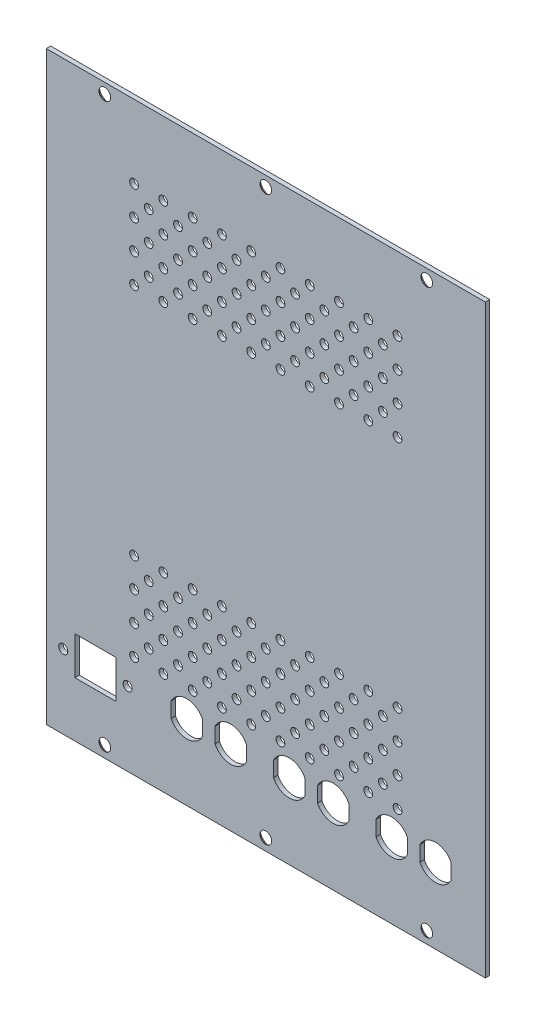
SolidWorks part; units mm, degrees
ref_plane "Спереди" through (0, 0, 0) normal (0, 0, 1) x (1, 0, 0)
ref_plane "Сверху" through (0, 0, 0) normal (0, 1, 0) x (1, 0, 0)
ref_plane "Справа" through (0, 0, 0) normal (1, 0, 0) x (0, 0, -1)
sketch "Эскиз1" plane through (0, 0, 0) normal (0, 0, 1) x (1, 0, 0)
  line L1 (0, 0) -> (150, 0)
  line L2 (0, 0) -> (0, 200)
  line L3 (0, 200) -> (150, 200)
  line L4 (150, 0) -> (150, 200)
  dimension "D1" = 150
  dimension "D2" = 200
extrude "Бобышка-Вытянуть1" add sketch "Эскиз1" along normal blind 1.5
sketch "Эскиз2" plane through (0, 0, 1.5) normal (0, 0, 1) x (1, 0, 0)
  line L0 (0, 0) -> (150, 0) construction
  line L1 (0, 200) -> (0, 0) construction
  line L2 (150, 200) -> (0, 200) construction
  circle A0 centre (20, 196.5) radius 2
  circle A1 centre (20, 4) radius 2
  circle A2 centre (75, 196.5) radius 2
  circle A3 centre (75, 4) radius 2
  circle A4 centre (130, 196.5) radius 2
  circle A5 centre (130, 4) radius 2
  dimension "D1" = 4
  dimension "D2" = 4
  dimension "D3" = 20
  dimension "D4" = 3.5
  dimension "D5" = 3
extrude "Вырез-Вытянуть1" cut sketch "Эскиз2" against normal through all
sketch "Эскиз3" plane through (0, 0, 1.5) normal (0, 0, 1) x (1, 0, 0)
  line L0 (0, 200) -> (0, 0) construction
  line L1 (0, 0) -> (150, 0) construction
  circle A0 centre (30, 35) radius 1.5
  circle A1 centre (40, 35) radius 1.5
  circle A2 centre (50, 35) radius 1.5
  circle A3 centre (60, 35) radius 1.5
  circle A4 centre (70, 35) radius 1.5
  circle A5 centre (80, 35) radius 1.5
  circle A6 centre (90, 35) radius 1.5
  circle A7 centre (100, 35) radius 1.5
  circle A8 centre (110, 35) radius 1.5
  circle A9 centre (120, 35) radius 1.5
  circle A10 centre (30, 45) radius 1.5
  circle A11 centre (40, 45) radius 1.5
  circle A12 centre (50, 45) radius 1.5
  circle A13 centre (60, 45) radius 1.5
  circle A14 centre (70, 45) radius 1.5
  circle A15 centre (80, 45) radius 1.5
  circle A16 centre (90, 45) radius 1.5
  circle A17 centre (100, 45) radius 1.5
  circle A18 centre (110, 45) radius 1.5
  circle A19 centre (120, 45) radius 1.5
  circle A20 centre (30, 55) radius 1.5
  circle A21 centre (40, 55) radius 1.5
  circle A22 centre (50, 55) radius 1.5
  circle A23 centre (60, 55) radius 1.5
  circle A24 centre (70, 55) radius 1.5
  circle A25 centre (80, 55) radius 1.5
  circle A26 centre (90, 55) radius 1.5
  circle A27 centre (100, 55) radius 1.5
  circle A28 centre (110, 55) radius 1.5
  circle A29 centre (120, 55) radius 1.5
  circle A30 centre (30, 65) radius 1.5
  circle A31 centre (40, 65) radius 1.5
  circle A32 centre (50, 65) radius 1.5
  circle A33 centre (60, 65) radius 1.5
  circle A34 centre (70, 65) radius 1.5
  circle A35 centre (80, 65) radius 1.5
  circle A36 centre (90, 65) radius 1.5
  circle A37 centre (100, 65) radius 1.5
  circle A38 centre (110, 65) radius 1.5
  circle A39 centre (120, 65) radius 1.5
  circle A40 centre (35, 40) radius 1.5
  circle A41 centre (45, 40) radius 1.5
  circle A42 centre (55, 40) radius 1.5
  circle A43 centre (65, 40) radius 1.5
  circle A44 centre (75, 40) radius 1.5
  circle A45 centre (85, 40) radius 1.5
  circle A46 centre (95, 40) radius 1.5
  circle A47 centre (105, 40) radius 1.5
  circle A48 centre (115, 40) radius 1.5
  circle A49 centre (45, 50) radius 1.5
  circle A50 centre (55, 50) radius 1.5
  circle A51 centre (65, 50) radius 1.5
  circle A52 centre (75, 50) radius 1.5
  circle A53 centre (85, 50) radius 1.5
  circle A54 centre (95, 50) radius 1.5
  circle A55 centre (105, 50) radius 1.5
  circle A56 centre (115, 50) radius 1.5
  circle A57 centre (45, 60) radius 1.5
  circle A58 centre (55, 60) radius 1.5
  circle A59 centre (65, 60) radius 1.5
  circle A60 centre (75, 60) radius 1.5
  circle A61 centre (85, 60) radius 1.5
  circle A62 centre (95, 60) radius 1.5
  circle A63 centre (105, 60) radius 1.5
  circle A64 centre (115, 60) radius 1.5
  circle A65 centre (35, 50) radius 1.5
  circle A66 centre (35, 60) radius 1.5
  circle A67 centre (30, 145) radius 1.5
  circle A68 centre (40, 145) radius 1.5
  circle A69 centre (50, 145) radius 1.5
  circle A70 centre (60, 145) radius 1.5
  circle A71 centre (70, 145) radius 1.5
  circle A72 centre (80, 145) radius 1.5
  circle A73 centre (90, 145) radius 1.5
  circle A74 centre (100, 145) radius 1.5
  circle A75 centre (110, 145) radius 1.5
  circle A76 centre (120, 145) radius 1.5
  circle A77 centre (30, 155) radius 1.5
  circle A78 centre (40, 155) radius 1.5
  circle A79 centre (50, 155) radius 1.5
  circle A80 centre (60, 155) radius 1.5
  circle A81 centre (70, 155) radius 1.5
  circle A82 centre (80, 155) radius 1.5
  circle A83 centre (90, 155) radius 1.5
  circle A84 centre (100, 155) radius 1.5
  circle A85 centre (110, 155) radius 1.5
  circle A86 centre (120, 155) radius 1.5
  circle A87 centre (30, 165) radius 1.5
  circle A88 centre (40, 165) radius 1.5
  circle A89 centre (50, 165) radius 1.5
  circle A90 centre (60, 165) radius 1.5
  circle A91 centre (70, 165) radius 1.5
  circle A92 centre (80, 165) radius 1.5
  circle A93 centre (90, 165) radius 1.5
  circle A94 centre (100, 165) radius 1.5
  circle A95 centre (110, 165) radius 1.5
  circle A96 centre (120, 165) radius 1.5
  circle A97 centre (30, 175) radius 1.5
  circle A98 centre (40, 175) radius 1.5
  circle A99 centre (50, 175) radius 1.5
  circle A100 centre (60, 175) radius 1.5
  circle A101 centre (70, 175) radius 1.5
  circle A102 centre (80, 175) radius 1.5
  circle A103 centre (90, 175) radius 1.5
  circle A104 centre (100, 175) radius 1.5
  circle A105 centre (110, 175) radius 1.5
  circle A106 centre (120, 175) radius 1.5
  circle A107 centre (35, 150) radius 1.5
  circle A108 centre (45, 150) radius 1.5
  circle A109 centre (55, 150) radius 1.5
  circle A110 centre (65, 150) radius 1.5
  circle A111 centre (75, 150) radius 1.5
  circle A112 centre (85, 150) radius 1.5
  circle A113 centre (95, 150) radius 1.5
  circle A114 centre (105, 150) radius 1.5
  circle A115 centre (115, 150) radius 1.5
  circle A116 centre (45, 160) radius 1.5
  circle A117 centre (55, 160) radius 1.5
  circle A118 centre (65, 160) radius 1.5
  circle A119 centre (75, 160) radius 1.5
  circle A120 centre (85, 160) radius 1.5
  circle A121 centre (95, 160) radius 1.5
  circle A122 centre (105, 160) radius 1.5
  circle A123 centre (115, 160) radius 1.5
  circle A124 centre (45, 170) radius 1.5
  circle A125 centre (55, 170) radius 1.5
  circle A126 centre (65, 170) radius 1.5
  circle A127 centre (75, 170) radius 1.5
  circle A128 centre (85, 170) radius 1.5
  circle A129 centre (95, 170) radius 1.5
  circle A130 centre (105, 170) radius 1.5
  circle A131 centre (115, 170) radius 1.5
  circle A132 centre (35, 160) radius 1.5
  circle A133 centre (35, 170) radius 1.5
  dimension "D1" = 3
  dimension "D2" = 30
  dimension "D3" = 35
  dimension "D5" = 4
  dimension "D6" = 5
  dimension "D7" = 5
  dimension "D4" = 10
  dimension "D8" = 9
  dimension "D9" = 3
  dimension "D10" = 2
extrude "Вырез-Вытянуть2" cut sketch "Эскиз3" against normal through all
sketch "Эскиз4" plane through (0, 0, 0) normal (0, 0, -1) x (-1, 0, 0)
  line L0 (-150, 0) -> (-150, 200) construction
  line L1 (0, 0) -> (-150, 0) construction
  circle A0 centre (-48, 25) radius 4.85
  circle A1 centre (-133, 25) radius 4.85
  circle A2 centre (-118, 25) radius 4.85
  circle A3 centre (-83, 25) radius 4.85
  circle A4 centre (-98, 25) radius 4.85
  circle A5 centre (-63, 25) radius 4.85
  dimension "D1" = 9.7
  dimension "D2" = 17
  dimension "D3" = 25
  dimension "D4" = 2
  dimension "D5" = 3
extrude "Вырез-Вытянуть3" cut sketch "Эскиз4" against normal through all
sketch "Эскиз5" plane through (0, 0, 0) normal (0, 0, -1) x (-1, 0, 0)
  line L0 (-131, 13) -> (-116.6472, 13) construction
  line L1 (-96, 13) -> (-81.6472, 13) construction
  line L2 (0, 0) -> (-150, 0) construction
  line L3 (-73, 13) -> (-10.6742, 13) construction
  circle A0 centre (-133, 25) radius 4.85 construction
  circle A1 centre (-98, 25) radius 4.85 construction
  circle A2 centre (-63, 25) radius 4.85 construction
  text T0 "24V" font "GOST Type BU" height 5
  text T1 "10V" font "GOST type B" height 5
  text T2 "мультиметр" font "GOST type B" height 5
  dimension "D1" = 13
  dimension "D2" = 2
  dimension "D3" = 2
  dimension "D4" = 10
extrude "Вырез-Вытянуть4" cut sketch "Эскиз5" against normal blind 0.5
sketch "Эскиз8" plane through (0, 0, 0) normal (0, 0, -1) x (-1, 0, 0)
  line L0 (0, 200) -> (0, 0) construction
  line L1 (-21, 31.05) -> (-10, 31.05)
  line L2 (-21, 31.05) -> (-21, 18.95)
  line L3 (-21, 18.95) -> (-10, 18.95)
  line L4 (-10, 31.05) -> (-10, 18.95)
  circle A1 centre (-48, 25) radius 4.85 construction
  point P6 (-21, 25)
  dimension "D1" = 10
  dimension "D2" = 0
  dimension "D3" = 11
  dimension "D4" = 12.1
extrude "Вырез-Вытянуть5" cut sketch "Эскиз8" against normal through all
sketch "Эскиз9" plane through (0, 0, 0) normal (0, 0, -1) x (-1, 0, 0)
  line L0 (-22.5, 10.95) -> (-5.209, 10.95) construction
  line L1 (-21, 18.95) -> (-10, 18.95) construction
  line L2 (-21, 31.05) -> (-21, 18.95) construction
  text T0 "USB" font "GOST type B" height 6
  dimension "D1" = 8
  dimension "D2" = 1.5
extrude "Вырез-Вытянуть6" cut sketch "Эскиз9" against normal up to surface (0.5 mm away) up to face at (36.6786, 14.7184, 0.5)
chamfer "Фаска1" distance 1.4 angle 45 6 edges at (22, 4, 0) (77, 4, 0) (132, 4, 0) (22, 196.5, 0) (77, 196.5, 0) (132, 196.5, 0)
sketch "Эскиз10" plane through (0, 0, 0) normal (0, 0, -1) x (-1, 0, 0)
  line L0 (0, 0) -> (-150, 0) construction
  line L1 (-103.35, 28.3038) -> (-103.35, 23.0962)
  line L2 (-138.35, 35.1494) -> (-127.65, 35.1494) construction
  line L3 (-138.35, 28.3038) -> (-138.35, 23.0962)
  line L4 (-138.35, 18.1769) -> (-127.65, 18.1769) construction
  line L5 (-127.65, 28.3038) -> (-127.65, 23.0962)
  line L6 (-123.35, 36.7729) -> (-112.65, 36.7729) construction
  line L7 (-123.35, 28.3038) -> (-123.35, 23.0962)
  line L8 (-123.35, 17.0454) -> (-112.65, 17.0454) construction
  line L9 (-112.65, 28.3038) -> (-112.65, 23.0962)
  line L10 (-92.65, 28.3038) -> (-92.65, 23.0962)
  line L11 (-88.35, 28.3038) -> (-88.35, 23.0962)
  line L12 (-77.65, 28.3038) -> (-77.65, 23.0962)
  line L13 (-68.35, 28.3038) -> (-68.35, 23.0962)
  line L14 (-57.65, 28.3038) -> (-57.65, 23.0962)
  line L15 (-53.35, 28.3038) -> (-53.35, 23.0962)
  line L16 (-42.65, 28.3038) -> (-42.65, 23.0962)
  arc A0 (-138.35, 23.0962) -> (-127.65, 23.0962) centre (-133, 25.7) ccw
  arc A1 (-112.65, 28.3038) -> (-123.35, 28.3038) centre (-118, 25.7) ccw
  arc A2 (-127.65, 28.3038) -> (-138.35, 28.3038) centre (-133, 25.7) ccw
  circle A3 centre (-133, 25) radius 4.85 construction
  circle A4 centre (-118, 25) radius 4.85 construction
  arc A5 (-123.35, 23.0962) -> (-112.65, 23.0962) centre (-118, 25.7) ccw
  arc A6 (-92.65, 28.3038) -> (-103.35, 28.3038) centre (-98, 25.7) ccw
  arc A7 (-103.35, 23.0962) -> (-92.65, 23.0962) centre (-98, 25.7) ccw
  arc A8 (-77.65, 28.3038) -> (-88.35, 28.3038) centre (-83, 25.7) ccw
  arc A9 (-88.35, 23.0962) -> (-77.65, 23.0962) centre (-83, 25.7) ccw
  arc A10 (-57.65, 28.3038) -> (-68.35, 28.3038) centre (-63, 25.7) ccw
  arc A11 (-68.35, 23.0962) -> (-57.65, 23.0962) centre (-63, 25.7) ccw
  arc A12 (-42.65, 28.3038) -> (-53.35, 28.3038) centre (-48, 25.7) ccw
  arc A13 (-53.35, 23.0962) -> (-42.65, 23.0962) centre (-48, 25.7) ccw
  point P14 (-133, 18.1769)
  point P22 (-118, 17.0454)
  dimension "D1" = 11.9
  dimension "D5" = 10.7
  dimension "D7" = 0
  dimension "D2" = 0
  dimension "D3" = 0
  dimension "D4" = 25.7
  dimension "D6" = 0
  dimension "D8" = 3
extrude "Вырез-Вытянуть7" cut sketch "Эскиз10" against normal through all
sketch "Эскиз11" plane through (0, 0, 0) normal (0, 0, -1) x (-1, 0, 0)
  line L0 (-21, 18.95) -> (-10, 18.95) construction
  line L1 (-23.8, 31.75) -> (-9.8, 31.75)
  line L2 (-23.8, 31.75) -> (-23.8, 18.75)
  line L3 (-23.8, 18.75) -> (-9.8, 18.75)
  line L4 (-9.8, 31.75) -> (-9.8, 18.75)
  line L5 (-10, 18.95) -> (-10, 31.05) construction
  point P4 (-23.4568, 18.5694)
  dimension "D1" = 14
  dimension "D2" = 13
  dimension "D3" = 0.2
  dimension "D4" = 0.2
extrude "Вырез-Вытянуть8" cut sketch "Эскиз11" against normal through all
sketch "Эскиз12" plane through (0, 0, 0) normal (0, 0, -1) x (-1, 0, 0)
  line L0 (-23.8, 31.75) -> (-23.8, 18.75) construction
  line L1 (-23.8, 18.75) -> (-9.8, 18.75) construction
  line L2 (-16.8, 31.75) -> (-16.8, 18.75) construction
  line L3 (-9.8, 31.75) -> (-23.8, 31.75) construction
  circle A0 centre (-27.8, 25.25) radius 1.55
  circle A1 centre (-5.8, 25.25) radius 1.55
  point P4 (-23.8, 25.25)
  point P7 (-16.8, 18.75)
  dimension "D1" = 3.1
  dimension "D2" = 0
  dimension "D3" = 11
extrude "Вырез-Вытянуть9" cut sketch "Эскиз12" against normal through all
